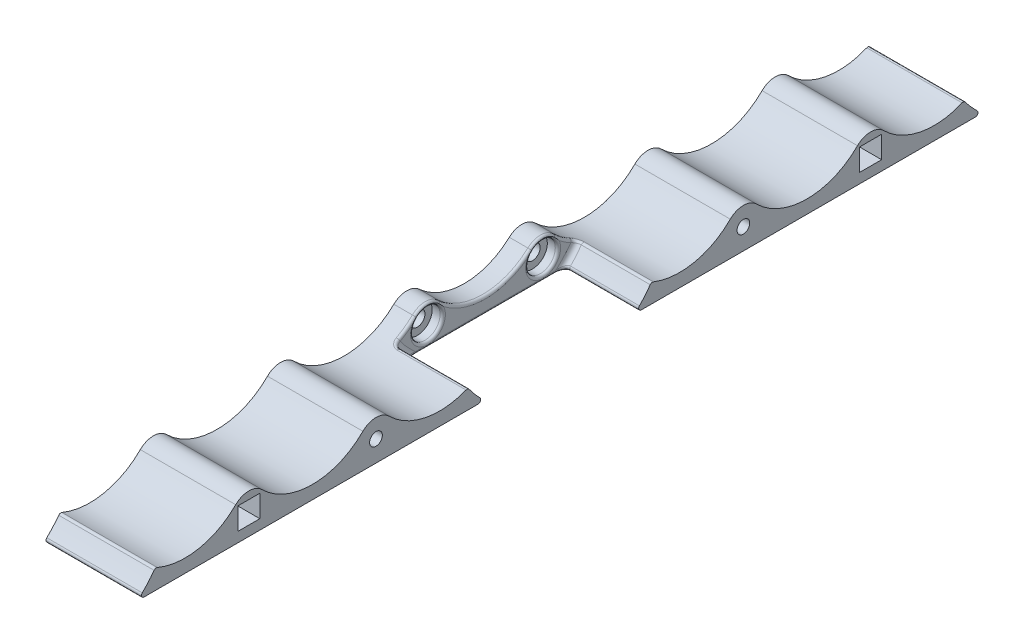
SolidWorks part; units mm, degrees
ref_plane "Front Plane" through (0, 0, 0) normal (0, 0, 1) x (1, 0, 0)
ref_plane "Top Plane" through (0, 0, 0) normal (0, 1, 0) x (1, 0, 0)
ref_plane "Right Plane" through (0, 0, 0) normal (1, 0, 0) x (0, 0, -1)
sketch "Sketch1" plane through (0, 0, 0) normal (1, 0, 0) x (0, 0, -1)
  line L0 (-126.5656, -24.6062) -> (126.5656, -24.6062)
  arc A0 (126.5656, -24.6062) -> (121.1052, -18.6881) centre (148.1579, 0.7938) cw
  arc A1 (-126.5656, -24.6062) -> (-121.1052, -18.6881) centre (-148.1579, 0.7937) ccw
  circle A2 centre (-93.1246, -18.3223) radius 5.5562 construction
  arc A3 (-93.1246, -9.0244) -> (-55.0246, -9.0244) centre (-74.0746, 0.7938) ccw construction
  circle A4 centre (-55.0246, -18.3223) radius 5.5562 construction
  arc A5 (-55.0246, -9.0244) -> (-17.2998, -9.7206) centre (-35.9746, 0.7938) ccw construction
  circle A6 centre (-17.2515, -18.6426) radius 5.5562 construction
  arc A7 (-17.2998, -9.7206) -> (17.2998, -9.7206) centre (0, 0) ccw construction
  circle A8 centre (17.2515, -18.6426) radius 5.5562 construction
  arc A9 (17.2998, -9.7206) -> (55.0246, -9.0244) centre (35.9746, 0.7937) ccw construction
  circle A10 centre (55.0246, -18.3223) radius 5.5562 construction
  circle A11 centre (93.1246, -18.3223) radius 5.5562 construction
  arc A12 (93.1246, -9.0244) -> (131.0767, -9.3061) centre (112.1746, 0.7937) ccw construction
  arc A13 (55.0246, -9.0244) -> (93.1246, -9.0244) centre (74.0746, 0.7937) ccw construction
  arc A14 (-89.2025, -14.3866) -> (-97.0466, -14.3866) centre (-93.1246, -18.3223) ccw
  arc A15 (-89.2025, -14.3866) -> (-58.9466, -14.3866) centre (-74.0746, 0.7938) ccw
  arc A16 (-51.1025, -14.3866) -> (-58.9466, -14.3866) centre (-55.0246, -18.3223) ccw
  arc A17 (-51.1025, -14.3866) -> (-21.1062, -14.641) centre (-35.9746, 0.7938) ccw
  arc A18 (-13.4777, -14.5645) -> (-21.1062, -14.641) centre (-17.2515, -18.6426) ccw
  arc A19 (-13.4777, -14.5645) -> (13.4777, -14.5645) centre (0, 0) ccw
  arc A20 (21.1062, -14.641) -> (13.4777, -14.5645) centre (17.2515, -18.6426) ccw
  arc A21 (21.1062, -14.641) -> (51.1025, -14.3866) centre (35.9746, 0.7937) ccw
  arc A22 (58.9466, -14.3866) -> (51.1025, -14.3866) centre (55.0246, -18.3223) ccw
  arc A23 (97.0466, -14.3866) -> (89.2025, -14.3866) centre (93.1246, -18.3223) ccw
  arc A24 (97.0466, -14.3866) -> (121.1052, -18.6881) centre (112.1746, 0.7937) ccw
  arc A25 (58.9466, -14.3866) -> (89.2025, -14.3866) centre (74.0746, 0.7937) ccw
  arc A26 (-131.0767, -9.3061) -> (-93.1246, -9.0244) centre (-112.1746, 0.7937) ccw construction
  arc A27 (-121.1052, -18.6881) -> (-97.0466, -14.3866) centre (-112.1746, 0.7937) ccw
  arc A28 (-121.4778, 20.7828) -> (-125.0548, 24.8278) centre (-148.1579, 0.7937) ccw construction
  point P3 (0, -24.6062)
  point P9 (148.1579, 0.7938)
  dimension "D1" = 24.6062
extrude "Boss-Extrude1" add sketch "Sketch1" along normal up to surface (28.575 mm away)
sketch "Sketch2" plane through (28.575, 0, 0) normal (1, 0, 0) x (0, 0, -1)
  circle A0 centre (0, 0) radius 33.3375
  arc A1 (-22.2685, 24.8093) -> (-26.2326, 20.5727) centre (0, 0) ccw construction
extrude "Cut-Extrude1" cut sketch "Sketch2" against normal up to surface (22.225 mm away)
sketch "Sketch3" plane through (28.575, 0, 0) normal (1, 0, 0) x (0, 0, -1)
  line L9 (-89.8226, -15.0203) -> (-96.4266, -15.0203)
  line L10 (-89.8226, -21.6243) -> (-89.8226, -15.0203)
  line L11 (-96.4266, -21.6243) -> (-89.8226, -21.6243)
  line L12 (-96.4266, -15.0203) -> (-96.4266, -21.6243)
  line L13 (-89.8226, -15.0203) -> (-96.4266, -15.0203)
  line L14 (-89.8226, -21.6243) -> (-89.8226, -15.0203)
  line L15 (-96.4266, -21.6243) -> (-89.8226, -21.6243)
  line L16 (-96.4266, -15.0203) -> (-96.4266, -21.6243)
  line L22 (89.8226, -21.6243) -> (96.4266, -21.6243)
  line L23 (96.4266, -21.6243) -> (96.4266, -15.0203)
  line L24 (96.4266, -15.0203) -> (89.8226, -15.0203)
  line L25 (89.8226, -15.0203) -> (89.8226, -21.6243)
  line L26 (89.8226, -21.6243) -> (96.4266, -21.6243)
  line L27 (96.4266, -21.6243) -> (96.4266, -15.0203)
  line L28 (96.4266, -15.0203) -> (89.8226, -15.0203)
  line L29 (89.8226, -15.0203) -> (89.8226, -21.6243)
  dimension "D1" = 0.127
  dimension "D2" = 0.127
extrude "Cut-Extrude2" cut sketch "Sketch3" against normal through all
sketch "Sketch4" plane through (28.575, 0, 0) normal (1, 0, 0) x (0, 0, -1)
  point P0 (-55.0246, -18.3223)
  point P3 (55.0246, -18.3223)
hole_wizard "#8 Clearance Hole1" positions "Sketch4" profile "Sketch5" hole size "#8" standard "ANSI Inch" end condition up to next
sketch "Sketch5" plane through (28.575, -18.3223, 55.0246) normal (0, 1, 0) x (0, 0, -1)
  line L0 (0, 0) -> (0, 28.575)
  line L1 (0, 28.575) -> (1.905, 28.575)
  line L2 (1.905, 28.575) -> (1.905, 0)
  line L5 (1.905, 0) -> (0, 0)
  line L11 (0, -6.35) -> (0, 107.95) construction
  dimension "Thru Hole Dia." = 3.81
  dimension "Thru Hole Depth" = 28.575
sketch "Sketch6" plane through (6.35, 0, 0) normal (1, 0, 0) x (0, 0, -1)
  circle A0 centre (-17.2515, -18.6426) radius 4.445
  circle A1 centre (17.2515, -18.6426) radius 4.445
  dimension "D1" = 8.89
extrude "Cut-Extrude3" cut sketch "Sketch6" against normal blind 3.175
sketch "Sketch7" plane through (3.175, 0, 0) normal (1, 0, 0) x (0, 0, -1)
  point P0 (-17.2515, -18.6426)
  point P3 (17.2515, -18.6426)
hole_wizard "#8 Clearance Hole2" positions "Sketch7" profile "Sketch8" hole size "#8" standard "ANSI Inch" end condition up to next
sketch "Sketch8" plane through (3.175, -18.6426, 17.2515) normal (0, 1, 0) x (0, 0, -1)
  line L0 (0, 0) -> (0, 3.175)
  line L1 (0, 3.175) -> (2.286, 3.175)
  line L2 (2.286, 3.175) -> (2.286, 0)
  line L5 (2.286, 0) -> (0, 0)
  line L11 (0, -6.35) -> (0, 107.95) construction
  dimension "Thru Hole Dia." = 4.572
  dimension "Thru Hole Depth" = 3.175
fillet "Fillet1" radius 1.5875 2 edges at (6.35, -21.8856, -25.1478) (6.35, -21.8856, 25.1478)
fillet "Fillet2" radius 0.7937 20 edges at (18.2563, -18.8803, -27.4758) (6.7035, -18.6353, -26.9296) (6.35, -16.5891, -23.4393) (6.35, -13.0866, -17.3072) (18.2563, -18.8803, 27.4758) (6.9586, -18.7415, 27.1614) (6.35, -16.5891, 23.4393) (6.35, -13.0866, 17.3072) (18.2562, -24.6062, 22.4927) (6.8874, -24.6062, 21.9001) (18.2562, -24.6062, -22.4927) (7.1838, -24.6062, -22.2096) (6.35, -18.6426, -21.6965) (6.35, -18.6426, 12.8065) (6.35, -19.8437, 0) (6.35, -24.6062, 0) (14.2875, -24.6062, -126.5656) (14.2875, -18.6881, -121.1052) (14.2875, -24.6062, 126.5656) (14.2875, -18.6881, 121.1052)
